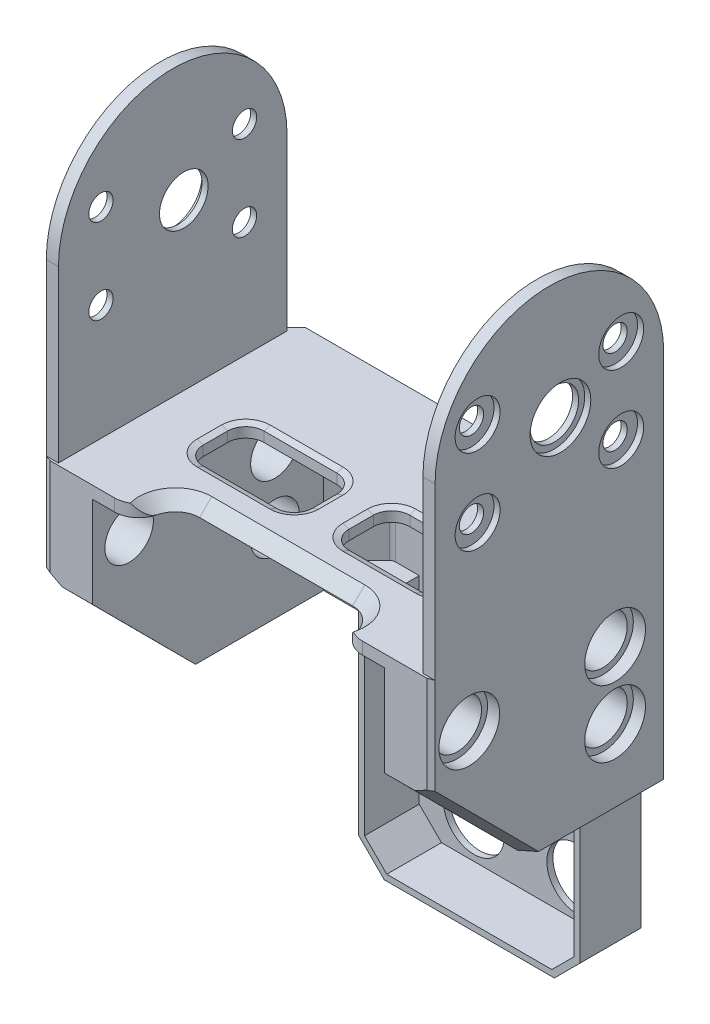
SolidWorks part; units mm, degrees
material "ABS"
ref_plane "Front Plane" through (0, 0, 0) normal (0, 0, 1) x (1, 0, 0)
ref_plane "Top Plane" through (0, 0, 0) normal (0, 1, 0) x (1, 0, 0)
ref_plane "Right Plane" through (0, 0, 0) normal (1, 0, 0) x (0, 0, -1)
sketch "Sketch1" plane through (0, 0, 0) normal (0, 0, 1) x (1, 0, 0)
  line L0 (-9.1213, -8.5) -> (-9.1213, -24.5)
  line L1 (-17, 8.5) -> (17, 8.5)
  line L2 (-17, 8.5) -> (-17, -8.5)
  line L3 (-17, -8.5) -> (-9.1213, -8.5)
  line L4 (17, 8.5) -> (17, -8.5)
  line L5 (-17, 8.5) -> (17, -8.5) construction
  line L6 (-17, -8.5) -> (17, 8.5) construction
  line L7 (-9.1213, -24.5) -> (-7, -26.6213)
  line L8 (-7, -26.6213) -> (7, -26.6213)
  line L9 (7, -26.6213) -> (9.1213, -24.5)
  line L10 (9.1213, -24.5) -> (9.1213, -8.5)
  line L11 (9.1213, -8.5) -> (17, -8.5)
  point P0 (0, 0)
  dimension "D1" = 34
  dimension "D2" = 17
  dimension "D3" = 16
  dimension "D4" = 14
  dimension "D5" = 3
extrude "Boss-Extrude1" add sketch "Sketch1" along normal mid plane 5
chamfer "Chamfer1" distance 6 angle 45 2 edges at (17, 0, -2.5) (-17, 0, -2.5)
chamfer "Chamfer2" distance 4 angle 45 1 edges at (0, 8.5, -2.5)
fillet "Fillet1" radius 1 1 edges at (11, -2, -2.5)
fillet "Fillet2" radius 1 1 edges at (-11, -2, -2.5)
chamfer "Chamfer3" distance 1 angle 20 2 edges at (-15.5, 8.5, 2) (15.5, 8.5, 2)
shell "Shell9" thickness 0.5
hole_wizard "Hole1" positions "Sketch2" profile "Sketch3" legacy
sketch "Sketch2" plane through (0, 0, -2.5) normal (0, 0, -1) x (-1, 0, 0)
  line L0 (7, -26.6213) -> (-7, -26.6213) construction
  line L1 (9.1213, -8.5) -> (9.1213, -24.5) construction
  line L2 (10.5858, 4.5) -> (-10.5858, 4.5) construction
  point P0 (-4.3787, 1.5)
  point P2 (4.1213, 1.5)
  point P4 (-4.3787, -6)
  point P6 (4.1213, -6)
  point P8 (-4.3787, -16.1213)
  point P10 (-4.3787, -23.1213)
  point P12 (4.1213, -23.1213)
  point P14 (4.1213, -16.1213)
  dimension "D1" = 3.5
  dimension "D2" = 5
  dimension "D3" = 7.5
  dimension "D4" = 3
  dimension "D5" = 8.5
  dimension "D6" = 7
sketch "Sketch3" plane through (4.3787, 1.5, -2.5) normal (1, 0, 0) x (0, 1, 0)
  line L0 (0, 0) -> (0, 25.2017)
  line L1 (0, 25.2017) -> (2, 24)
  line L2 (2, 24) -> (2, 1)
  line L3 (2, 1) -> (2.5, 1)
  line L4 (2.5, 0) -> (0, 0)
  line L5 (0, -11.3109) -> (0, 121.1557) construction
  line L6 (0, 25.2017) -> (-2, 24) construction
  line L7 (2.5, 1) -> (2.5, 0)
  dimension "Depth" = 24
  dimension "Drill Angle" = 118
  dimension "Diameter" = 4
  dimension "C-Bore Diameter" = 5
  dimension "C-Bore Depth" = 1
sketch "Sketch4" plane through (0, 0, 0) normal (1, 0, 0) x (0, 0, -1)
  line L0 (-2.5, 8.5) -> (-21.5, 8.5)
  line L1 (-21.5, 8.5) -> (-21.5, 0)
  line L2 (-2.5, -8.5) -> (-13.0295, -8.5)
  line L3 (-13.0295, -8.5) -> (-21.5, 0)
  line L4 (-2.5, 8.5) -> (-2.5, -8.5)
  dimension "D1" = 19
  dimension "D2" = 8.5
  dimension "D3" = 12
extrude "Boss-Extrude3" add sketch "Sketch4" against normal blind 4 from offset 16
hole_wizard "Hole2" positions "Sketch7" profile "Sketch8" legacy
sketch "Sketch7" plane through (16, 0, 0) normal (1, 0, 0) x (0, 0, -1)
  line L0 (-21.5, 8.5) -> (-21.5, 0) construction
  line L1 (-2.5, 8.5) -> (-21.5, 8.5) construction
  line L2 (-2.5, -8.5) -> (-2.5, 7.5) construction
  point P0 (-18.5, 3.5)
  point P2 (-6.5, 3.5)
  point P4 (-6.5, -2)
  dimension "D1" = 3
  dimension "D2" = 5
  dimension "D3" = 5
  dimension "D4" = 4
  dimension "D5" = 5.5
sketch "Sketch8" plane through (16, 3.5, 18.5) normal (0, 1, 0) x (0, 0, -1)
  line L0 (0, 0) -> (0, 5.2017)
  line L1 (0, 5.2017) -> (2, 4)
  line L2 (2, 4) -> (2, 1)
  line L3 (2, 1) -> (2.5, 1)
  line L4 (2.5, 0) -> (0, 0)
  line L5 (0, -11.3109) -> (0, 121.1557) construction
  line L6 (0, 5.2017) -> (-2, 4) construction
  line L7 (2.5, 1) -> (2.5, 0)
  dimension "Depth" = 4
  dimension "Drill Angle" = 118
  dimension "Diameter" = 4
  dimension "C-Bore Diameter" = 5
  dimension "C-Bore Depth" = 1
chamfer "Chamfer6" distance 1.5 angle 20 2 edges at (16, -8.5, 7.7647) (16, -4.25, 17.2647)
chamfer "Chamfer7" distance 0.5 angle 20 1 edges at (16, 4.6367, 21.5)
mirror "Mirror2" about plane through (0, 0, 0) normal (1, 0, 0) of "Chamfer7", "Chamfer6", "Hole2", "Boss-Extrude3"
sketch "Sketch9" plane through (0, 0, 0) normal (0, 1, 0) x (1, 0, 0)
  line L0 (12, -21.5) -> (10.2033, -21.5)
  line L1 (-12, -2.5) -> (12, -2.5)
  line L2 (-12, -2.5) -> (-12, -21.5)
  line L4 (12, -2.5) -> (12, -21.5)
  line L5 (8.2288, -19.8185) -> (8.2712, -20.0815)
  line L6 (6.2967, -18.4) -> (-6.2967, -18.4)
  line L7 (-8.2712, -20.0815) -> (-8.2288, -19.8185)
  line L8 (-10.2033, -21.5) -> (-12, -21.5)
  line L9 (12, -13.0295) -> (12, -2.5) construction
  line L10 (9, -15.4) -> (3, -15.4)
  line L11 (10.5, -13.9) -> (10.5, -11.9)
  line L12 (9, -10.4) -> (3, -10.4)
  line L13 (1.5, -13.9) -> (1.5, -11.9)
  line L14 (10.5, -15.4) -> (1.5, -10.4) construction
  line L15 (10.5, -10.4) -> (1.5, -15.4) construction
  line L16 (-3, -15.4) -> (-9, -15.4)
  line L17 (-1.5, -13.9) -> (-1.5, -11.9)
  line L18 (-3, -10.4) -> (-9, -10.4)
  line L19 (-10.5, -13.9) -> (-10.5, -11.9)
  line L20 (-1.5, -15.4) -> (-10.5, -10.4) construction
  line L21 (-1.5, -10.4) -> (-10.5, -15.4) construction
  line L23 (-12, -13.0295) -> (-12, -2.5) construction
  arc A0 (-8.2712, -20.0815) -> (-6.2967, -18.4) centre (-6.2967, -20.4) cw
  arc A1 (6.2967, -18.4) -> (8.2712, -20.0815) centre (6.2967, -20.4) cw
  arc A2 (-10.2033, -21.5) -> (-8.2288, -19.8185) centre (-10.2033, -19.5) ccw
  arc A3 (8.2288, -19.8185) -> (10.2033, -21.5) centre (10.2033, -19.5) ccw
  arc A4 (-10.5, -13.9) -> (-9, -15.4) centre (-9, -13.9) ccw
  arc A5 (-10.5, -11.9) -> (-9, -10.4) centre (-9, -11.9) cw
  arc A6 (-1.5, -13.9) -> (-3, -15.4) centre (-3, -13.9) cw
  arc A7 (-1.5, -11.9) -> (-3, -10.4) centre (-3, -11.9) ccw
  arc A8 (10.5, -13.9) -> (9, -15.4) centre (9, -13.9) cw
  arc A9 (1.5, -13.9) -> (3, -15.4) centre (3, -13.9) ccw
  arc A10 (1.5, -11.9) -> (3, -10.4) centre (3, -11.9) cw
  arc A11 (10.5, -11.9) -> (9, -10.4) centre (9, -11.9) ccw
  point P4 (-6, -12.9)
  point P19 (-8, -18.4)
  point P22 (8, -18.4)
  point P27 (8.5, -21.5)
  point P28 (6, -12.9)
  point P58 (0, 0)
  point P61 (0, 0)
  dimension "D4" = 2
  dimension "D13" = 1.5
  dimension "D14" = 1.5
  dimension "D1" = 3.5
  dimension "D2" = 7.9
  dimension "D3" = 16
  dimension "D5" = 1.5
  dimension "D6" = 3
  dimension "D7" = 9
  dimension "D8" = 3
  dimension "D9" = 1.5
  dimension "D10" = 5
  dimension "D11" = 9
  dimension "D12" = 5
extrude "Boss-Extrude4" add sketch "Sketch9" along normal blind 1 from offset 7.5
chamfer "Chamfer8" distance 0.5 angle 20 16 edges at (-10.5, 8.5, 12.9) (-10.0607, 8.5, 14.9607) (-10.0607, 8.5, 10.8393) (-6, 8.5, 15.4) (-6, 8.5, 10.4) (-1.9393, 8.5, 14.9607) (-1.9393, 8.5, 10.8393) (-1.5, 8.5, 12.9) (1.5, 8.5, 12.9) (1.9393, 8.5, 14.9607) (1.9393, 8.5, 10.8393) (6, 8.5, 15.4) (6, 8.5, 10.4) (10.0607, 8.5, 14.9607) (10.0607, 8.5, 10.8393) (10.5, 8.5, 12.9)
chamfer "Chamfer9" distance 1 angle 45 3 edges at (-7.5935, 8.5, 18.8773) (7.5935, 8.5, 18.8773) (0, 8.5, 18.4)
sketch "Sketch10" plane through (0, 0, 0) normal (1, 0, 0) x (0, 0, -1)
  line L0 (-21.318, 22.5) -> (-21.318, 8.5)
  line L1 (-2.5, 22.5) -> (-2.5, 8.5)
  line L2 (-2.5, 8.5) -> (-21.318, 8.5)
  arc A0 (-21.318, 22.5) -> (-2.5, 22.5) centre (-11.909, 22.5) cw
  point P3 (0, 0)
  point P5 (0, 0)
  dimension "D2" = 14
extrude "Boss-Extrude5" add sketch "Sketch10" along normal blind 1 from offset 15
hole_wizard "Hole3" positions "Sketch13" profile "Sketch14" legacy
sketch "Sketch13" plane through (16, 0, 0) normal (1, 0, 0) x (0, 0, -1)
  line L0 (-2.5, 7.5) -> (-2.5, 22.5) construction
  arc A0 (-2.5, 22.5) -> (-21.318, 22.5) centre (-11.909, 22.5) ccw construction
  point P0 (-11, 22.0832)
  dimension "D1" = 1
  dimension "D2" = 8.5
sketch "Sketch14" plane through (16, 22.0832, 11) normal (0, 1, 0) x (0, 0, -1)
  line L0 (0, 0) -> (0, 4.2017)
  line L1 (0, 4.2017) -> (2, 3)
  line L2 (2, 3) -> (2, 0.5)
  line L3 (2, 0.5) -> (2.5, 0.5)
  line L4 (2.5, 0) -> (0, 0)
  line L5 (0, -11.3109) -> (0, 121.1557) construction
  line L6 (0, 4.2017) -> (-2, 3) construction
  line L7 (2.5, 0.5) -> (2.5, 0)
  dimension "Depth" = 3
  dimension "Drill Angle" = 118
  dimension "Diameter" = 4
  dimension "C-Bore Diameter" = 5
  dimension "C-Bore Depth" = 0.5
hole_wizard "Hole4" positions "Sketch15" profile "Sketch16" legacy
sketch "Sketch15" plane through (16, 0, 0) normal (1, 0, 0) x (0, 0, -1)
  line L0 (-21.318, 22.5) -> (-21.318, 8.5) construction
  line L1 (-2.5, 7.5) -> (-2.5, 22.5) construction
  arc A0 (-2.5, 22.5) -> (-21.318, 22.5) centre (-11.909, 22.5) ccw construction
  point P0 (-17.818, 25)
  point P2 (-6, 25)
  point P4 (-17.818, 18)
  point P6 (-6, 18)
  dimension "D1" = 3.5
  dimension "D2" = 3.5
  dimension "D3" = 7
  dimension "D4" = 2.5
sketch "Sketch16" plane through (16, 25, 17.818) normal (0, 1, 0) x (0, 0, -1)
  line L0 (0, 0) -> (0, 1.6009)
  line L1 (0, 1.6009) -> (1, 1)
  line L2 (1, 1) -> (1, 0.5)
  line L3 (1, 0.5) -> (1.85, 0.5)
  line L4 (1.85, 0) -> (0, 0)
  line L5 (0, -11.3109) -> (0, 121.1557) construction
  line L6 (0, 1.6009) -> (-1, 1) construction
  line L7 (1.85, 0.5) -> (1.85, 0)
  dimension "Depth" = 1
  dimension "Drill Angle" = 118
  dimension "Diameter" = 2
  dimension "C-Bore Diameter" = 3.7
  dimension "C-Bore Depth" = 0.5
mirror "Mirror3" about plane through (0, 0, 0) normal (1, 0, 0) of "Hole4", "Hole3", "Boss-Extrude5"
equation "\"80eg\"=50"
